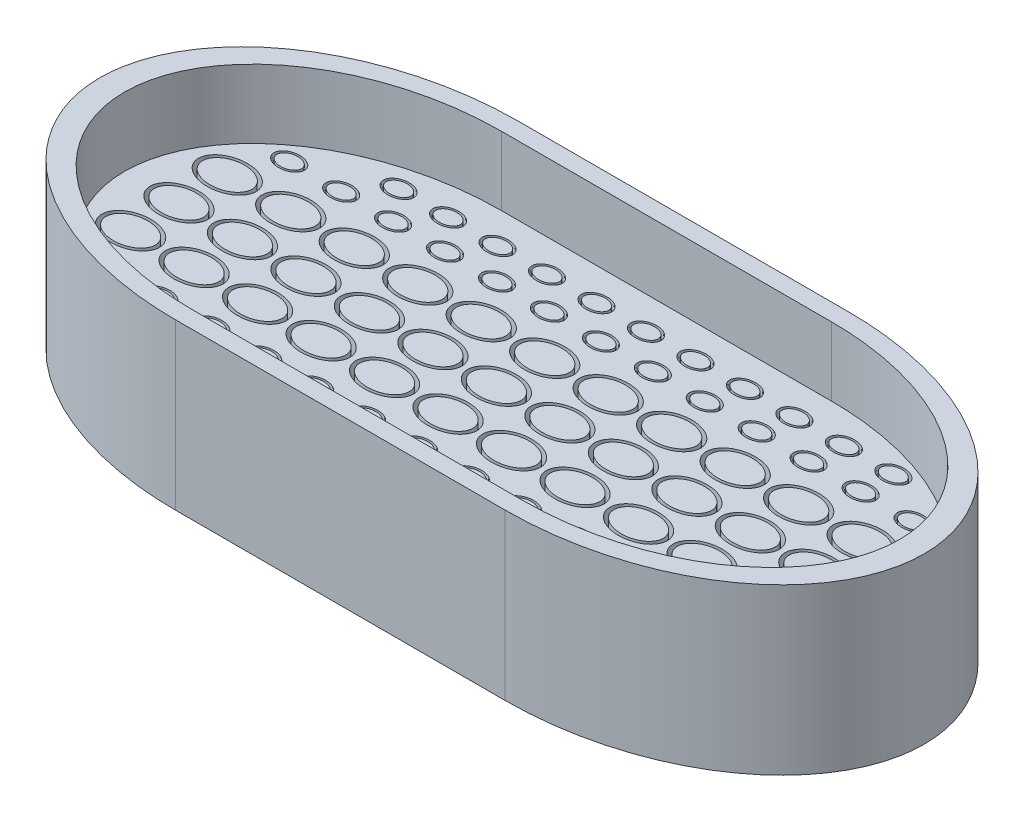
SolidWorks part; units mm, degrees
note: The reader was unsure of these and kept them because the rebuilt part matched: shared geometry of "Sketch1<3>".
ref_plane "Front Plane" through (0, 0, 0) normal (0, 0, 1) x (1, 0, 0)
ref_plane "Top Plane" through (0, 0, 0) normal (0, 1, 0) x (1, 0, 0)
ref_plane "Right Plane" through (0, 0, 0) normal (1, 0, 0) x (0, 0, -1)
sketch "Sketch1" plane through (0, 0, 0) normal (0, 1, 0) x (1, 0, 0)
  line L0 (-10, 0) -> (10, 0) construction
  line L1 (-10, 15) -> (10, 15)
  line L2 (-10, -15) -> (10, -15)
  line L3 (-10, 13.5) -> (10, 13.5)
  line L4 (-10, -13.5) -> (10, -13.5)
  line L5 (-1000, 0) -> (49000, 0) construction
  arc A0 (-10, 15) -> (-10, -15) centre (-10, 0) ccw
  arc A1 (10, -15) -> (10, 15) centre (10, 0) ccw
  arc A2 (10, -13.5) -> (10, 13.5) centre (10, 0) ccw
  arc A3 (-10, 13.5) -> (-10, -13.5) centre (-10, 0) ccw
  circle A16 centre (-20.1957, -4.2213) radius 1.5
  circle A22 centre (-19.0225, -7.9425) radius 0.75
  circle A32 centre (-20.1957, -4.2213) radius 1.75
  circle A33 centre (-19.0225, -7.9425) radius 0.925
  circle A34 centre (-15.8725, -7.9425) radius 0.925
  circle A35 centre (-15.8725, -7.9425) radius 0.75
  circle A36 centre (-12.7225, -7.9425) radius 0.925
  circle A37 centre (-12.7225, -7.9425) radius 0.75
  circle A38 centre (-9.5725, -7.9425) radius 0.925
  circle A39 centre (-9.5725, -7.9425) radius 0.75
  circle A40 centre (-6.4225, -7.9425) radius 0.925
  circle A41 centre (-6.4225, -7.9425) radius 0.75
  circle A42 centre (-3.2725, -7.9425) radius 0.925
  circle A43 centre (-3.2725, -7.9425) radius 0.75
  circle A44 centre (-0.1225, -7.9425) radius 0.925
  circle A45 centre (-0.1225, -7.9425) radius 0.75
  circle A46 centre (3.0275, -7.9425) radius 0.925
  circle A47 centre (3.0275, -7.9425) radius 0.75
  circle A48 centre (6.1775, -7.9425) radius 0.925
  circle A49 centre (6.1775, -7.9425) radius 0.75
  circle A50 centre (9.3275, -7.9425) radius 0.925
  circle A51 centre (9.3275, -7.9425) radius 0.75
  circle A52 centre (12.4775, -7.9425) radius 0.925
  circle A53 centre (12.4775, -7.9425) radius 0.75
  circle A54 centre (15.6275, -7.9425) radius 0.925
  circle A55 centre (15.6275, -7.9425) radius 0.75
  circle A56 centre (18.7775, -7.9425) radius 0.925
  circle A57 centre (18.7775, -7.9425) radius 0.75
  circle A58 centre (-16.3457, -4.2213) radius 1.5
  circle A59 centre (-16.3457, -4.2213) radius 1.75
  circle A60 centre (-12.4957, -4.2213) radius 1.5
  circle A61 centre (-12.4957, -4.2213) radius 1.75
  circle A62 centre (-8.6457, -4.2213) radius 1.5
  circle A63 centre (-8.6457, -4.2213) radius 1.75
  circle A64 centre (-4.7957, -4.2213) radius 1.5
  circle A65 centre (-4.7957, -4.2213) radius 1.75
  circle A66 centre (-0.9457, -4.2213) radius 1.5
  circle A67 centre (-0.9457, -4.2213) radius 1.75
  circle A68 centre (2.9043, -4.2213) radius 1.5
  circle A69 centre (2.9043, -4.2213) radius 1.75
  circle A70 centre (6.7543, -4.2213) radius 1.5
  circle A71 centre (6.7543, -4.2213) radius 1.75
  circle A72 centre (10.6043, -4.2213) radius 1.5
  circle A73 centre (10.6043, -4.2213) radius 1.75
  circle A74 centre (14.4543, -4.2213) radius 1.5
  circle A75 centre (14.4543, -4.2213) radius 1.75
  circle A76 centre (18.3043, -4.2213) radius 1.5
  circle A77 centre (18.3043, -4.2213) radius 1.75
  circle A80 centre (-15.8725, 7.9425) radius 0.75
  circle A81 centre (-15.8725, 7.9425) radius 0.925
  circle A82 centre (-19.0225, 7.9425) radius 0.925
  circle A83 centre (-19.0225, 7.9425) radius 0.75
  circle A84 centre (-9.5725, 7.9425) radius 0.75
  circle A85 centre (-9.5725, 7.9425) radius 0.925
  circle A86 centre (-12.7225, 7.9425) radius 0.75
  circle A87 centre (-12.7225, 7.9425) radius 0.925
  circle A88 centre (-3.2725, 7.9425) radius 0.75
  circle A89 centre (-3.2725, 7.9425) radius 0.925
  circle A90 centre (-6.4225, 7.9425) radius 0.75
  circle A91 centre (-6.4225, 7.9425) radius 0.925
  circle A92 centre (3.0275, 7.9425) radius 0.75
  circle A93 centre (3.0275, 7.9425) radius 0.925
  circle A94 centre (-0.1225, 7.9425) radius 0.75
  circle A95 centre (-0.1225, 7.9425) radius 0.925
  circle A96 centre (18.7775, 7.9425) radius 0.75
  circle A97 centre (18.7775, 7.9425) radius 0.925
  circle A98 centre (15.6275, 7.9425) radius 0.75
  circle A99 centre (15.6275, 7.9425) radius 0.925
  circle A100 centre (12.4775, 7.9425) radius 0.75
  circle A101 centre (12.4775, 7.9425) radius 0.925
  circle A102 centre (9.3275, 7.9425) radius 0.75
  circle A103 centre (9.3275, 7.9425) radius 0.925
  circle A104 centre (6.1775, 7.9425) radius 0.75
  circle A105 centre (6.1775, 7.9425) radius 0.925
  circle A108 centre (18.3043, 4.2213) radius 1.75
  circle A109 centre (18.3043, 4.2213) radius 1.5
  circle A110 centre (14.4543, 4.2213) radius 1.75
  circle A111 centre (14.4543, 4.2213) radius 1.5
  circle A112 centre (10.6043, 4.2213) radius 1.75
  circle A113 centre (10.6043, 4.2213) radius 1.5
  circle A114 centre (6.7543, 4.2213) radius 1.75
  circle A115 centre (6.7543, 4.2213) radius 1.5
  circle A116 centre (2.9043, 4.2213) radius 1.75
  circle A117 centre (2.9043, 4.2213) radius 1.5
  circle A118 centre (-0.9457, 4.2213) radius 1.75
  circle A119 centre (-0.9457, 4.2213) radius 1.5
  circle A120 centre (-4.7957, 4.2213) radius 1.75
  circle A121 centre (-4.7957, 4.2213) radius 1.5
  circle A122 centre (-8.6457, 4.2213) radius 1.75
  circle A123 centre (-8.6457, 4.2213) radius 1.5
  circle A124 centre (-12.4957, 4.2213) radius 1.75
  circle A125 centre (-12.4957, 4.2213) radius 1.5
  circle A126 centre (-16.3457, 4.2213) radius 1.75
  circle A127 centre (-16.3457, 4.2213) radius 1.5
  circle A128 centre (-20.1957, 4.2213) radius 1.75
  circle A129 centre (-20.1957, 4.2213) radius 1.5
  circle A130 centre (22.1543, -4.2213) radius 1.5 [skipped]
  circle A131 centre (22.1543, -4.2213) radius 1.75 [skipped]
  circle A132 centre (-14.2706, -10.6543) radius 0.925
  circle A133 centre (-14.2706, -10.6543) radius 0.75
  circle A134 centre (-20.1957, 0) radius 1.5
  circle A135 centre (-20.1957, 0) radius 1.75
  circle A136 centre (-16.3457, 0) radius 1.5
  circle A137 centre (-16.3457, 0) radius 1.75
  circle A138 centre (-12.4957, 0) radius 1.5
  circle A139 centre (-12.4957, 0) radius 1.75
  circle A140 centre (-8.6457, 0) radius 1.5
  circle A141 centre (-8.6457, 0) radius 1.75
  circle A142 centre (-4.7957, 0) radius 1.5
  circle A143 centre (-4.7957, 0) radius 1.75
  circle A144 centre (-0.9457, 0) radius 1.5
  circle A145 centre (-0.9457, 0) radius 1.75
  circle A146 centre (2.9043, 0) radius 1.5
  circle A147 centre (2.9043, 0) radius 1.75
  circle A148 centre (6.7543, 0) radius 1.5
  circle A149 centre (6.7543, 0) radius 1.75
  circle A150 centre (10.6043, 0) radius 1.5
  circle A151 centre (10.6043, 0) radius 1.75
  circle A152 centre (14.4543, 0) radius 1.5
  circle A153 centre (14.4543, 0) radius 1.75
  circle A154 centre (18.3043, 0) radius 1.5
  circle A155 centre (18.3043, 0) radius 1.75
  circle A156 centre (-11.2706, -10.6543) radius 0.925
  circle A157 centre (-11.2706, -10.6543) radius 0.75
  circle A158 centre (-8.2706, -10.6543) radius 0.925
  circle A159 centre (-8.2706, -10.6543) radius 0.75
  circle A160 centre (-5.2706, -10.6543) radius 0.925
  circle A161 centre (-5.2706, -10.6543) radius 0.75
  circle A162 centre (-2.2706, -10.6543) radius 0.925
  circle A163 centre (-2.2706, -10.6543) radius 0.75
  circle A164 centre (0.7294, -10.6543) radius 0.925
  circle A165 centre (0.7294, -10.6543) radius 0.75
  circle A166 centre (3.7294, -10.6543) radius 0.925
  circle A167 centre (3.7294, -10.6543) radius 0.75
  circle A168 centre (6.7294, -10.6543) radius 0.925
  circle A169 centre (6.7294, -10.6543) radius 0.75
  circle A170 centre (9.7294, -10.6543) radius 0.925
  circle A171 centre (9.7294, -10.6543) radius 0.75
  circle A172 centre (12.7294, -10.6543) radius 0.925
  circle A173 centre (12.7294, -10.6543) radius 0.75
  circle A174 centre (15.7294, -10.6543) radius 0.925
  circle A175 centre (15.7294, -10.6543) radius 0.75
  circle A176 centre (15.7294, 10.6543) radius 0.75
  circle A177 centre (15.7294, 10.6543) radius 0.925
  circle A178 centre (12.7294, 10.6543) radius 0.75
  circle A179 centre (12.7294, 10.6543) radius 0.925
  circle A180 centre (9.7294, 10.6543) radius 0.75
  circle A181 centre (9.7294, 10.6543) radius 0.925
  circle A182 centre (6.7294, 10.6543) radius 0.75
  circle A183 centre (6.7294, 10.6543) radius 0.925
  circle A184 centre (3.7294, 10.6543) radius 0.75
  circle A185 centre (3.7294, 10.6543) radius 0.925
  circle A186 centre (0.7294, 10.6543) radius 0.75
  circle A187 centre (0.7294, 10.6543) radius 0.925
  circle A188 centre (-2.2706, 10.6543) radius 0.75
  circle A189 centre (-2.2706, 10.6543) radius 0.925
  circle A190 centre (-5.2706, 10.6543) radius 0.75
  circle A191 centre (-5.2706, 10.6543) radius 0.925
  circle A192 centre (-8.2706, 10.6543) radius 0.75
  circle A193 centre (-8.2706, 10.6543) radius 0.925
  circle A194 centre (-11.2706, 10.6543) radius 0.75
  circle A195 centre (-11.2706, 10.6543) radius 0.925
  circle A196 centre (-14.2706, 10.6543) radius 0.75
  circle A197 centre (-14.2706, 10.6543) radius 0.925
  point P3 (0, 0)
  point P8 (-25, 0)
  point P9 (25, 0)
  dimension "D4" = 0.25
  dimension "D5" = 1.5
  dimension "D6" = 3
  dimension "D1" = 30
  dimension "D2" = 50
  dimension "D3" = 1.5
  dimension "D7" = 0.175
  dimension "D8" = 13
  dimension "D9" = 12
  dimension "D10" = 11
  dimension "D11" = 11
extrude "Boss-Extrude1" add sketch "Sketch1" along normal blind 7 contours L3 A3 L4 A2 A174 A172 A170 A168 A166 A164 A162 A160 A158 A156 A155 A153 A151 A149 A147 A145 A143 A141 A139 A137 A135 A132 A126 | A32 | A59 | A33 | A34 | A61 | A36 | A38 | A40 | A42 | A63 | A65 | A67 | A44 | A69 | A46 | A71 | A48 | A50 | A73 | A52 | A75 | A77 | A54 | A56 | A108 | A110 | A112 | A114 | A116 | A118 | A120 | A122 | A124 | A128 | A82 | A81 | A87 | A85 | A91 | A89 | A95 | A93 | A105 | A103 | A101 | A99 | A97 | A177 | A179 | A181 | A183 | A185 | A187 | A197 | A195 | A193 | A191 | A189
extrude "Boss-Extrude2" add sketch "Sketch1<3>" along normal blind 12 contours L2 A1 L1 A0 A3 L3 A2 L4
sketch "Sketch1<3>" plane through (0, 0, 0) normal (0, 1, 0) x (1, 0, 0) same geometry as "Sketch1"
sketch "Sketch2" plane through (0, 7, 0) normal (0, 1, 0) x (1, 0, 0)
  line L2 (10, 13.5) -> (-10, 13.5)
  line L6 (10, 13.5) -> (-10, 13.5)
  line L7 (-10, -13.5) -> (10, -13.5)
  line L8 (10, 13.5) -> (-10, 13.5)
  line L9 (-10, -13.5) -> (10, -13.5)
  line L10 (10, 15) -> (-10, 15)
  line L11 (-10, -15) -> (10, -15)
  line L12 (10, 15) -> (-10, 15)
  line L13 (-10, -15) -> (10, -15)
  line L14 (10, 13.5) -> (-10, 13.5)
  line L16 (-10, -13.5) -> (10, -13.5)
  line L17 (-10, -13.5) -> (10, -13.5)
  circle A1 centre (-16.3457, -4.2213) radius 1.75
  arc A2 (-10, 13.5) -> (-10, -13.5) centre (-10, 0) ccw
  arc A6 (10, -13.5) -> (10, 13.5) centre (10, 0) ccw
  arc A7 (-10, 13.5) -> (-10, -13.5) centre (-10, 0) ccw
  arc A8 (10, -13.5) -> (10, 13.5) centre (10, 0) ccw
  arc A9 (-10, 13.5) -> (-10, -13.5) centre (-10, 0) ccw
  arc A10 (10, -15) -> (10, 15) centre (10, 0) ccw
  arc A11 (-10, 15) -> (-10, -15) centre (-10, 0) ccw
  arc A12 (10, -15) -> (10, 15) centre (10, 0) ccw
  arc A13 (-10, 15) -> (-10, -15) centre (-10, 0) ccw
  circle A14 centre (-16.3457, -4.2213) radius 1.75
  circle A15 centre (-12.7225, -7.9425) radius 0.75
  circle A16 centre (-12.7225, -7.9425) radius 0.75
  circle A17 centre (-12.7225, -7.9425) radius 0.925
  circle A18 centre (-12.7225, -7.9425) radius 0.925
  circle A19 centre (-15.8725, -7.9425) radius 0.75
  circle A20 centre (-15.8725, -7.9425) radius 0.75
  circle A21 centre (-15.8725, -7.9425) radius 0.925
  circle A22 centre (-15.8725, -7.9425) radius 0.925
  circle A23 centre (-19.0225, -7.9425) radius 0.925
  circle A24 centre (-19.0225, -7.9425) radius 0.925
  circle A25 centre (-20.1957, -4.2213) radius 1.75
  circle A26 centre (-20.1957, -4.2213) radius 1.75
  circle A27 centre (-0.1225, -7.9425) radius 0.925
  circle A28 centre (-0.1225, -7.9425) radius 0.925
  circle A29 centre (-3.2725, -7.9425) radius 0.75
  circle A30 centre (-3.2725, -7.9425) radius 0.75
  circle A31 centre (-3.2725, -7.9425) radius 0.925
  circle A32 centre (-3.2725, -7.9425) radius 0.925
  circle A33 centre (-6.4225, -7.9425) radius 0.75
  circle A34 centre (-6.4225, -7.9425) radius 0.75
  circle A35 centre (-6.4225, -7.9425) radius 0.925
  circle A36 centre (-6.4225, -7.9425) radius 0.925
  circle A37 centre (-9.5725, -7.9425) radius 0.75
  circle A38 centre (-9.5725, -7.9425) radius 0.75
  circle A39 centre (-9.5725, -7.9425) radius 0.925
  circle A40 centre (-9.5725, -7.9425) radius 0.925
  circle A41 centre (-20.1957, -4.2213) radius 1.5
  circle A42 centre (-20.1957, -4.2213) radius 1.5
  circle A43 centre (9.3275, -7.9425) radius 0.75
  circle A44 centre (9.3275, -7.9425) radius 0.75
  circle A45 centre (9.3275, -7.9425) radius 0.925
  circle A46 centre (9.3275, -7.9425) radius 0.925
  circle A47 centre (6.1775, -7.9425) radius 0.75
  circle A48 centre (6.1775, -7.9425) radius 0.75
  circle A49 centre (6.1775, -7.9425) radius 0.925
  circle A50 centre (6.1775, -7.9425) radius 0.925
  circle A51 centre (3.0275, -7.9425) radius 0.75
  circle A52 centre (3.0275, -7.9425) radius 0.75
  circle A53 centre (3.0275, -7.9425) radius 0.925
  circle A54 centre (3.0275, -7.9425) radius 0.925
  circle A55 centre (-0.1225, -7.9425) radius 0.75
  circle A56 centre (-0.1225, -7.9425) radius 0.75
  circle A57 centre (-19.0225, -7.9425) radius 0.75
  circle A58 centre (-19.0225, -7.9425) radius 0.75
  circle A59 centre (-12.4957, -4.2213) radius 1.75
  circle A60 centre (-12.4957, -4.2213) radius 1.75
  circle A61 centre (-16.3457, -4.2213) radius 1.5
  circle A62 centre (-16.3457, -4.2213) radius 1.5
  circle A63 centre (18.7775, -7.9425) radius 0.75
  circle A64 centre (18.7775, -7.9425) radius 0.75
  circle A65 centre (18.7775, -7.9425) radius 0.925
  circle A66 centre (18.7775, -7.9425) radius 0.925
  circle A67 centre (15.6275, -7.9425) radius 0.75
  circle A68 centre (15.6275, -7.9425) radius 0.75
  circle A69 centre (15.6275, -7.9425) radius 0.925
  circle A70 centre (15.6275, -7.9425) radius 0.925
  circle A71 centre (12.4775, -7.9425) radius 0.75
  circle A72 centre (12.4775, -7.9425) radius 0.75
  circle A73 centre (12.4775, -7.9425) radius 0.925
  circle A74 centre (12.4775, -7.9425) radius 0.925
  circle A75 centre (2.9043, -4.2213) radius 1.75
  circle A76 centre (2.9043, -4.2213) radius 1.75
  circle A77 centre (-0.9457, -4.2213) radius 1.75
  circle A78 centre (-0.9457, -4.2213) radius 1.75
  circle A79 centre (-0.9457, -4.2213) radius 1.5
  circle A80 centre (-0.9457, -4.2213) radius 1.5
  circle A81 centre (-4.7957, -4.2213) radius 1.75
  circle A82 centre (-4.7957, -4.2213) radius 1.75
  circle A83 centre (-4.7957, -4.2213) radius 1.5
  circle A84 centre (-4.7957, -4.2213) radius 1.5
  circle A85 centre (-8.6457, -4.2213) radius 1.75
  circle A86 centre (-8.6457, -4.2213) radius 1.75
  circle A87 centre (-8.6457, -4.2213) radius 1.5
  circle A88 centre (-8.6457, -4.2213) radius 1.5
  circle A89 centre (-12.4957, -4.2213) radius 1.5
  circle A90 centre (-12.4957, -4.2213) radius 1.5
  circle A91 centre (18.3043, -4.2213) radius 1.75
  circle A92 centre (18.3043, -4.2213) radius 1.75
  circle A93 centre (14.4543, -4.2213) radius 1.75
  circle A94 centre (14.4543, -4.2213) radius 1.75
  circle A95 centre (14.4543, -4.2213) radius 1.5
  circle A96 centre (14.4543, -4.2213) radius 1.5
  circle A97 centre (10.6043, -4.2213) radius 1.75
  circle A98 centre (10.6043, -4.2213) radius 1.75
  circle A99 centre (10.6043, -4.2213) radius 1.5
  circle A100 centre (10.6043, -4.2213) radius 1.5
  circle A101 centre (6.7543, -4.2213) radius 1.75
  circle A102 centre (6.7543, -4.2213) radius 1.75
  circle A103 centre (6.7543, -4.2213) radius 1.5
  circle A104 centre (6.7543, -4.2213) radius 1.5
  circle A105 centre (2.9043, -4.2213) radius 1.5
  circle A106 centre (2.9043, -4.2213) radius 1.5
  circle A107 centre (-9.5725, 7.9425) radius 0.925
  circle A108 centre (-9.5725, 7.9425) radius 0.925
  circle A109 centre (-9.5725, 7.9425) radius 0.75
  circle A110 centre (-9.5725, 7.9425) radius 0.75
  circle A111 centre (-19.0225, 7.9425) radius 0.75
  circle A112 centre (-19.0225, 7.9425) radius 0.75
  circle A113 centre (-19.0225, 7.9425) radius 0.925
  circle A114 centre (-19.0225, 7.9425) radius 0.925
  circle A115 centre (-15.8725, 7.9425) radius 0.925
  circle A116 centre (-15.8725, 7.9425) radius 0.925
  circle A117 centre (-15.8725, 7.9425) radius 0.75
  circle A118 centre (-15.8725, 7.9425) radius 0.75
  circle A119 centre (18.3043, -4.2213) radius 1.5
  circle A120 centre (18.3043, -4.2213) radius 1.5
  circle A121 centre (-0.1225, 7.9425) radius 0.925
  circle A122 centre (-0.1225, 7.9425) radius 0.925
  circle A123 centre (-0.1225, 7.9425) radius 0.75
  circle A124 centre (-0.1225, 7.9425) radius 0.75
  circle A125 centre (3.0275, 7.9425) radius 0.925
  circle A126 centre (3.0275, 7.9425) radius 0.925
  circle A127 centre (3.0275, 7.9425) radius 0.75
  circle A128 centre (3.0275, 7.9425) radius 0.75
  circle A129 centre (-6.4225, 7.9425) radius 0.925
  circle A130 centre (-6.4225, 7.9425) radius 0.925
  circle A131 centre (-6.4225, 7.9425) radius 0.75
  circle A132 centre (-6.4225, 7.9425) radius 0.75
  circle A133 centre (-3.2725, 7.9425) radius 0.925
  circle A134 centre (-3.2725, 7.9425) radius 0.925
  circle A135 centre (-3.2725, 7.9425) radius 0.75
  circle A136 centre (-3.2725, 7.9425) radius 0.75
  circle A137 centre (-12.7225, 7.9425) radius 0.925
  circle A138 centre (-12.7225, 7.9425) radius 0.925
  circle A139 centre (-12.7225, 7.9425) radius 0.75
  circle A140 centre (-12.7225, 7.9425) radius 0.75
  circle A141 centre (6.1775, 7.9425) radius 0.925
  circle A142 centre (6.1775, 7.9425) radius 0.925
  circle A143 centre (6.1775, 7.9425) radius 0.75
  circle A144 centre (6.1775, 7.9425) radius 0.75
  circle A145 centre (9.3275, 7.9425) radius 0.925
  circle A146 centre (9.3275, 7.9425) radius 0.925
  circle A147 centre (9.3275, 7.9425) radius 0.75
  circle A148 centre (9.3275, 7.9425) radius 0.75
  circle A149 centre (12.4775, 7.9425) radius 0.925
  circle A150 centre (12.4775, 7.9425) radius 0.925
  circle A151 centre (12.4775, 7.9425) radius 0.75
  circle A152 centre (12.4775, 7.9425) radius 0.75
  circle A153 centre (15.6275, 7.9425) radius 0.925
  circle A154 centre (15.6275, 7.9425) radius 0.925
  circle A155 centre (15.6275, 7.9425) radius 0.75
  circle A156 centre (15.6275, 7.9425) radius 0.75
  circle A157 centre (18.7775, 7.9425) radius 0.925
  circle A158 centre (18.7775, 7.9425) radius 0.925
  circle A159 centre (18.7775, 7.9425) radius 0.75
  circle A160 centre (18.7775, 7.9425) radius 0.75
  circle A161 centre (2.9043, 4.2213) radius 1.5
  circle A162 centre (2.9043, 4.2213) radius 1.5
  circle A163 centre (2.9043, 4.2213) radius 1.75
  circle A164 centre (2.9043, 4.2213) radius 1.75
  circle A165 centre (6.7543, 4.2213) radius 1.5
  circle A166 centre (6.7543, 4.2213) radius 1.5
  circle A167 centre (6.7543, 4.2213) radius 1.75
  circle A168 centre (6.7543, 4.2213) radius 1.75
  circle A169 centre (10.6043, 4.2213) radius 1.5
  circle A170 centre (10.6043, 4.2213) radius 1.5
  circle A171 centre (10.6043, 4.2213) radius 1.75
  circle A172 centre (10.6043, 4.2213) radius 1.75
  circle A173 centre (14.4543, 4.2213) radius 1.5
  circle A174 centre (14.4543, 4.2213) radius 1.5
  circle A175 centre (14.4543, 4.2213) radius 1.75
  circle A176 centre (14.4543, 4.2213) radius 1.75
  circle A177 centre (18.3043, 4.2213) radius 1.5
  circle A178 centre (18.3043, 4.2213) radius 1.5
  circle A179 centre (18.3043, 4.2213) radius 1.75
  circle A180 centre (18.3043, 4.2213) radius 1.75
  circle A181 centre (-16.3457, 4.2213) radius 1.5
  circle A182 centre (-16.3457, 4.2213) radius 1.5
  circle A183 centre (-16.3457, 4.2213) radius 1.75
  circle A184 centre (-16.3457, 4.2213) radius 1.75
  circle A185 centre (-12.4957, 4.2213) radius 1.5
  circle A186 centre (-12.4957, 4.2213) radius 1.5
  circle A187 centre (-12.4957, 4.2213) radius 1.75
  circle A188 centre (-12.4957, 4.2213) radius 1.75
  circle A189 centre (-8.6457, 4.2213) radius 1.5
  circle A190 centre (-8.6457, 4.2213) radius 1.5
  circle A191 centre (-8.6457, 4.2213) radius 1.75
  circle A192 centre (-8.6457, 4.2213) radius 1.75
  circle A193 centre (-4.7957, 4.2213) radius 1.5
  circle A194 centre (-4.7957, 4.2213) radius 1.5
  circle A195 centre (-4.7957, 4.2213) radius 1.75
  circle A196 centre (-4.7957, 4.2213) radius 1.75
  circle A197 centre (-0.9457, 4.2213) radius 1.5
  circle A198 centre (-0.9457, 4.2213) radius 1.5
  circle A199 centre (-0.9457, 4.2213) radius 1.75
  circle A200 centre (-0.9457, 4.2213) radius 1.75
  circle A201 centre (-20.1957, 4.2213) radius 1.5
  circle A202 centre (-20.1957, 4.2213) radius 1.5
  circle A203 centre (-20.1957, 4.2213) radius 1.75
  circle A204 centre (-20.1957, 4.2213) radius 1.75
  circle A205 centre (-2.2706, 10.6543) radius 0.925
  arc A206 (-10, 13.5) -> (-10, -13.5) centre (-10, 0) ccw
  arc A207 (10, -13.5) -> (10, 13.5) centre (10, 0) ccw
  arc A208 (10, -13.5) -> (10, 13.5) centre (10, 0) ccw
  circle A209 centre (-2.2706, 10.6543) radius 0.925
  circle A210 centre (-2.2706, 10.6543) radius 0.75
  circle A211 centre (-2.2706, 10.6543) radius 0.75
  circle A212 centre (0.7294, 10.6543) radius 0.925
  circle A213 centre (0.7294, 10.6543) radius 0.925
  circle A214 centre (0.7294, 10.6543) radius 0.75
  circle A216 centre (0.7294, 10.6543) radius 0.75
  circle A218 centre (3.7294, 10.6543) radius 0.925
  circle A220 centre (3.7294, 10.6543) radius 0.925
  circle A222 centre (3.7294, 10.6543) radius 0.75
  circle A224 centre (3.7294, 10.6543) radius 0.75
  circle A226 centre (6.7294, 10.6543) radius 0.925
  circle A228 centre (6.7294, 10.6543) radius 0.925
  circle A230 centre (6.7294, 10.6543) radius 0.75
  circle A232 centre (6.7294, 10.6543) radius 0.75
  circle A233 centre (9.7294, 10.6543) radius 0.925
  circle A234 centre (9.7294, 10.6543) radius 0.925
  circle A235 centre (9.7294, 10.6543) radius 0.75
  circle A236 centre (9.7294, 10.6543) radius 0.75
  circle A237 centre (-14.2706, 10.6543) radius 0.925
  circle A246 centre (-14.2706, 10.6543) radius 0.925
  circle A247 centre (-14.2706, 10.6543) radius 0.75
  circle A248 centre (-14.2706, 10.6543) radius 0.75
  circle A249 centre (-11.2706, 10.6543) radius 0.925
  circle A250 centre (-11.2706, 10.6543) radius 0.925
  circle A251 centre (-11.2706, 10.6543) radius 0.75
  circle A252 centre (-11.2706, 10.6543) radius 0.75
  circle A253 centre (-8.2706, 10.6543) radius 0.925
  circle A254 centre (-8.2706, 10.6543) radius 0.925
  circle A255 centre (-8.2706, 10.6543) radius 0.75
  circle A256 centre (-8.2706, 10.6543) radius 0.75
  circle A257 centre (-5.2706, 10.6543) radius 0.925
  circle A258 centre (-5.2706, 10.6543) radius 0.925
  circle A259 centre (-5.2706, 10.6543) radius 0.75
  circle A260 centre (-5.2706, 10.6543) radius 0.75
  circle A355 centre (-16.3457, 0) radius 1.75
  circle A356 centre (-16.3457, 0) radius 1.75
  circle A357 centre (-14.2706, -10.6543) radius 0.925
  circle A358 centre (-14.2706, -10.6543) radius 0.925
  circle A393 centre (-16.3457, 0) radius 1.5
  circle A394 centre (-16.3457, 0) radius 1.5
  circle A395 centre (-14.2706, -10.6543) radius 0.75
  circle A396 centre (-14.2706, -10.6543) radius 0.75
  circle A417 centre (-20.1957, 0) radius 1.75
  circle A418 centre (-20.1957, 0) radius 1.75
  circle A459 centre (-4.7957, 0) radius 1.75
  circle A460 centre (-4.7957, 0) radius 1.75
  circle A461 centre (-8.6457, 0) radius 1.75
  circle A462 centre (-8.6457, 0) radius 1.75
  circle A463 centre (-8.6457, 0) radius 1.5
  circle A464 centre (-8.6457, 0) radius 1.5
  circle A465 centre (-12.4957, 0) radius 1.75
  circle A466 centre (-12.4957, 0) radius 1.75
  circle A467 centre (-12.4957, 0) radius 1.5
  circle A468 centre (-12.4957, 0) radius 1.5
  circle A469 centre (-20.1957, 0) radius 1.5
  circle A470 centre (-20.1957, 0) radius 1.5
  circle A475 centre (14.4543, 0) radius 1.75
  circle A476 centre (14.4543, 0) radius 1.75
  circle A477 centre (10.6043, 0) radius 1.75
  circle A478 centre (10.6043, 0) radius 1.75
  circle A479 centre (10.6043, 0) radius 1.5
  circle A480 centre (10.6043, 0) radius 1.5
  circle A481 centre (6.7543, 0) radius 1.75
  circle A482 centre (6.7543, 0) radius 1.75
  circle A483 centre (6.7543, 0) radius 1.5
  circle A484 centre (6.7543, 0) radius 1.5
  circle A485 centre (2.9043, 0) radius 1.75
  circle A486 centre (2.9043, 0) radius 1.75
  circle A487 centre (2.9043, 0) radius 1.5
  circle A488 centre (2.9043, 0) radius 1.5
  circle A489 centre (-0.9457, 0) radius 1.75
  circle A490 centre (-0.9457, 0) radius 1.75
  circle A491 centre (-0.9457, 0) radius 1.5
  circle A492 centre (-0.9457, 0) radius 1.5
  circle A493 centre (-4.7957, 0) radius 1.5
  circle A494 centre (-4.7957, 0) radius 1.5
  circle A495 centre (-5.2706, -10.6543) radius 0.75
  circle A496 centre (-5.2706, -10.6543) radius 0.75
  circle A497 centre (-5.2706, -10.6543) radius 0.925
  circle A498 centre (-5.2706, -10.6543) radius 0.925
  circle A499 centre (-8.2706, -10.6543) radius 0.75
  circle A500 centre (-8.2706, -10.6543) radius 0.75
  circle A501 centre (-8.2706, -10.6543) radius 0.925
  circle A502 centre (-8.2706, -10.6543) radius 0.925
  circle A503 centre (-11.2706, -10.6543) radius 0.75
  circle A504 centre (-11.2706, -10.6543) radius 0.75
  circle A505 centre (-11.2706, -10.6543) radius 0.925
  circle A506 centre (-11.2706, -10.6543) radius 0.925
  circle A507 centre (18.3043, 0) radius 1.75
  circle A508 centre (18.3043, 0) radius 1.75
  circle A509 centre (18.3043, 0) radius 1.5
  circle A510 centre (18.3043, 0) radius 1.5
  circle A511 centre (14.4543, 0) radius 1.5
  circle A512 centre (14.4543, 0) radius 1.5
  circle A513 centre (6.7294, -10.6543) radius 0.75
  circle A514 centre (6.7294, -10.6543) radius 0.75
  circle A515 centre (6.7294, -10.6543) radius 0.925
  circle A516 centre (6.7294, -10.6543) radius 0.925
  circle A517 centre (3.7294, -10.6543) radius 0.75
  circle A518 centre (3.7294, -10.6543) radius 0.75
  circle A519 centre (3.7294, -10.6543) radius 0.925
  circle A520 centre (3.7294, -10.6543) radius 0.925
  circle A521 centre (0.7294, -10.6543) radius 0.75
  circle A522 centre (0.7294, -10.6543) radius 0.75
  circle A523 centre (0.7294, -10.6543) radius 0.925
  circle A524 centre (0.7294, -10.6543) radius 0.925
  circle A525 centre (-2.2706, -10.6543) radius 0.75
  circle A526 centre (-2.2706, -10.6543) radius 0.75
  circle A527 centre (-2.2706, -10.6543) radius 0.925
  circle A528 centre (-2.2706, -10.6543) radius 0.925
  circle A529 centre (12.7294, 10.6543) radius 0.925
  circle A530 centre (12.7294, 10.6543) radius 0.925
  circle A531 centre (12.7294, 10.6543) radius 0.75
  circle A532 centre (12.7294, 10.6543) radius 0.75
  circle A533 centre (15.7294, 10.6543) radius 0.925
  circle A534 centre (15.7294, 10.6543) radius 0.925
  circle A535 centre (15.7294, 10.6543) radius 0.75
  circle A536 centre (15.7294, 10.6543) radius 0.75
  circle A537 centre (15.7294, -10.6543) radius 0.75
  circle A538 centre (15.7294, -10.6543) radius 0.75
  circle A539 centre (15.7294, -10.6543) radius 0.925
  circle A540 centre (15.7294, -10.6543) radius 0.925
  circle A541 centre (12.7294, -10.6543) radius 0.75
  circle A542 centre (12.7294, -10.6543) radius 0.75
  circle A543 centre (12.7294, -10.6543) radius 0.925
  circle A544 centre (12.7294, -10.6543) radius 0.925
  circle A545 centre (9.7294, -10.6543) radius 0.75
  circle A546 centre (9.7294, -10.6543) radius 0.75
  circle A547 centre (9.7294, -10.6543) radius 0.925
  circle A548 centre (9.7294, -10.6543) radius 0.925
  dimension "D1" = 0
  dimension "D2" = 0
  dimension "D3" = 0
  dimension "D4" = 0
  dimension "D5" = 0
  dimension "D6" = 0
  dimension "D7" = 0
  dimension "D8" = 0
  dimension "D9" = 0
  dimension "D10" = 0
  dimension "D11" = 0
  dimension "D12" = 0
  dimension "D13" = 0
  dimension "D14" = 0
  dimension "D15" = 0
  dimension "D16" = 0
  dimension "D17" = 0
  dimension "D18" = 0
  dimension "D19" = 0
  dimension "D20" = 0
  dimension "D21" = 0
  dimension "D22" = 0
  dimension "D23" = 0
  dimension "D24" = 0
  dimension "D25" = 0
  dimension "D26" = 0
  dimension "D27" = 0
  dimension "D28" = 0
  dimension "D29" = 0
  dimension "D30" = 0
  dimension "D31" = 0
  dimension "D32" = 0
  dimension "D33" = 0
  dimension "D34" = 0
  dimension "D35" = 0
  dimension "D36" = 0
  dimension "D37" = 0
  dimension "D38" = 0
  dimension "D39" = 0
  dimension "D40" = 0
  dimension "D41" = 0
  dimension "D42" = 0
  dimension "D43" = 0
  dimension "D44" = 0
  dimension "D45" = 0
  dimension "D46" = 0
  dimension "D47" = 0
  dimension "D48" = 0
  dimension "D49" = 0
  dimension "D50" = 0
  dimension "D51" = 0
  dimension "D52" = 0
  dimension "D53" = 0
  dimension "D54" = 0
  dimension "D55" = 0
  dimension "D56" = 0
  dimension "D57" = 0
  dimension "D58" = 0
  dimension "D59" = 0
  dimension "D60" = 0
  dimension "D61" = 0
  dimension "D62" = 0
  dimension "D63" = 0
  dimension "D64" = 0
  dimension "D65" = 0
  dimension "D66" = 0
  dimension "D67" = 0
  dimension "D68" = 0
  dimension "D69" = 0
  dimension "D70" = 0
  dimension "D71" = 0
  dimension "D72" = 0
  dimension "D73" = 0
  dimension "D74" = 0
  dimension "D75" = 0
  dimension "D76" = 0
  dimension "D77" = 0
  dimension "D78" = 0
  dimension "D79" = 0
  dimension "D80" = 0
  dimension "D81" = 0
  dimension "D82" = 0
  dimension "D83" = 0
  dimension "D84" = 0
  dimension "D85" = 0
  dimension "D86" = 0
  dimension "D87" = 0
  dimension "D88" = 0
  dimension "D89" = 0
  dimension "D90" = 0
  dimension "D91" = 0
  dimension "D92" = 0
  dimension "D93" = 0
  dimension "D94" = 0
  dimension "D95" = 0
  dimension "D96" = 0
  dimension "D97" = 0
  dimension "D98" = 0
  dimension "D99" = 0
  dimension "D100" = 0
  dimension "D101" = 0
  dimension "D102" = 0
  dimension "D103" = 0
  dimension "D104" = 0
  dimension "D105" = 0
  dimension "D106" = 0
  dimension "D107" = 0
  dimension "D108" = 0
  dimension "D109" = 0
  dimension "D112" = 0
  dimension "D113" = 0
  dimension "D114" = 0
  dimension "D115" = 0
  dimension "D116" = 0
  dimension "D117" = 0
  dimension "D118" = 0
  dimension "D119" = 0
  dimension "D167" = 0
  dimension "D168" = 0
  dimension "D186" = 0
  dimension "D187" = 0
  dimension "D198" = 0
  dimension "D219" = 0
  dimension "D220" = 0
  dimension "D221" = 0
  dimension "D222" = 0
  dimension "D223" = 0
  dimension "D224" = 0
  dimension "D227" = 0
  dimension "D228" = 0
  dimension "D229" = 0
  dimension "D230" = 0
  dimension "D231" = 0
  dimension "D232" = 0
  dimension "D233" = 0
  dimension "D234" = 0
  dimension "D235" = 0
  dimension "D236" = 0
  dimension "D237" = 0
  dimension "D238" = 0
  dimension "D239" = 0
  dimension "D240" = 0
  dimension "D241" = 0
  dimension "D242" = 0
  dimension "D243" = 0
  dimension "D244" = 0
  dimension "D245" = 0
  dimension "D246" = 0
  dimension "D247" = 0
  dimension "D248" = 0
  dimension "D249" = 0
  dimension "D250" = 0
  dimension "D251" = 0
  dimension "D252" = 0
  dimension "D253" = 0
  dimension "D254" = 0
  dimension "D255" = 0
  dimension "D256" = 0
  dimension "D257" = 0
  dimension "D258" = 0
  dimension "D259" = 0
  dimension "D260" = 0
  dimension "D261" = 0
  dimension "D262" = 0
  dimension "D263" = 0
extrude "Cut-Extrude2" cut sketch "Sketch2" against normal blind 5 contours A66 A64 | A70 A68 | A92 A120 | A94 A96 | A74 A72 | A46 A44 | A98 A100 | A102 A104 | A50 A48 | A54 A52 | A76 A106 | A28 A56 | A78 A80 | A32 A30 | A36 A34 | A82 A84 | A86 A88 | A40 A38 | A18 A16 | A60 A90 | A22 A20 | A14 A62 | A24 A58 | A26 A42 | A204 A202 | A184 A182 | A188 A186 | A192 A190 | A196 A194 | A200 A198 | A164 A162 | A168 A166 | A172 A170 | A180 A178 | A176 A174 | A158 A160 | A154 A156 | A150 A152 | A146 A148 | A142 A144 | A126 A128 | A122 A124 | A134 A136 | A130 A132 | A108 A110 | A138 A140 | A116 A118 | A114 A112 | A418 A470 | A356 A394 | A466 A468 | A462 A464 | A460 A494 | A490 A492 | A486 A488 | A482 A484 | A478 A480 | A476 A512 | A508 A510 | A534 A536 | A530 A532 | A234 A236 | A228 A232 | A220 A224 | A213 A216 | A209 A211 | A258 A260 | A254 A256 | A246 A248 | A250 A252 | A358 A396 | A506 A504 | A502 A500 | A498 A496 | A528 A526 | A524 A522 | A520 A518 | A516 A514 | A548 A546 | A544 A542 | A540 A538
scale "Scale1" scale about origin uniform scaling no x scale factor 1.2 y scale factor 1 z scale factor 0.833
